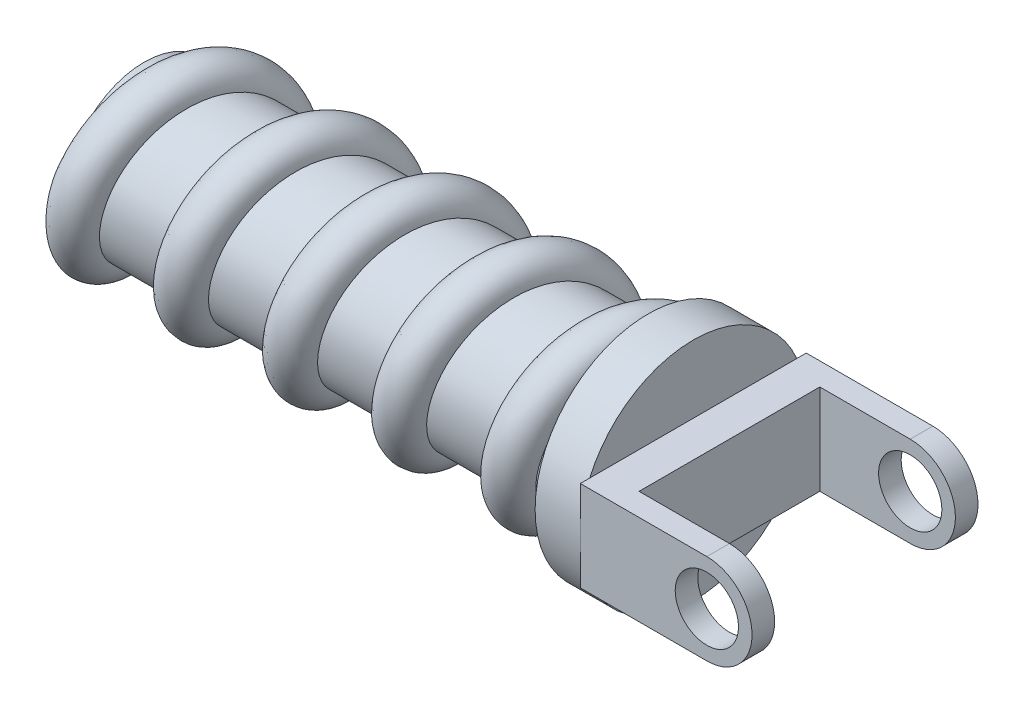
SolidWorks part; units mm, degrees
ref_plane "Front Plane" through (0, 0, 0) normal (0, 0, 1) x (1, 0, 0)
ref_plane "Top Plane" through (0, 0, 0) normal (0, 1, 0) x (1, 0, 0)
ref_plane "Right Plane" through (0, 0, 0) normal (1, 0, 0) x (0, 0, -1)
sketch "Sketch1" plane through (0, 0, 0) normal (0, 0, 1) x (1, 0, 0)
  line L1 (0, 0) -> (50.8, 0)
  line L2 (0, 0) -> (0, -5.08)
  line L3 (0, -5.08) -> (50.8, -5.08)
  line L4 (50.8, 0) -> (50.8, -5.08)
  dimension "D1" = 5.08
  dimension "D2" = 50.8
extrude "Boss-Extrude1" add sketch "Sketch1" along normal blind 7.62
sketch "Sketch2" plane through (0, 0, 7.62) normal (0, 0, 1) x (1, 0, 0)
  line L1 (0, 0) -> (0, -5.08) construction
  circle A0 centre (2.54, -2.54) radius 1.778
  point P8 (0, -2.54)
  dimension "D1" = 3.556
  dimension "D2" = 2.54
extrude "Boss-Extrude2" add sketch "Sketch2" along normal blind 5.08
sketch "Sketch3" plane through (0, 0, 0) normal (0, 0, -1) x (-1, 0, 0)
  circle A0 centre (-2.54, -2.54) radius 1.778
  dimension "D1" = 3.556
extrude "Boss-Extrude3" add sketch "Sketch3" along normal blind 5.08
sketch "Sketch4" plane through (0, 0, 7.62) normal (0, 0, 1) x (1, 0, 0)
  line L0 (0, -5.08) -> (50.8, -5.08) construction
  line L1 (50.8, 0) -> (48.768, 0)
  line L2 (50.8, 0) -> (50.8, -5.08)
  line L3 (50.8, -5.08) -> (48.768, -5.08)
  line L4 (48.768, 0) -> (48.768, -5.08)
  dimension "D1" = 2.032
extrude "Boss-Extrude4" add sketch "Sketch4" along normal blind 2.54
ref_plane "Plane1" through (0, 0, 10.16) normal (0, 0, 1) x (1, 0, 0)
sketch "Sketch5" plane through (0, 0, 10.16) normal (0, 0, 1) x (1, 0, 0)
  line L0 (48.768, -5.08) -> (50.8, -5.08) construction
  line L1 (50.8, 0) -> (55.88, 0)
  line L2 (50.8, 0) -> (50.8, -5.08)
  line L3 (50.8, -5.08) -> (55.88, -5.08)
  arc A0 (55.88, 0) -> (55.88, -5.08) centre (55.88, -2.54) cw
  dimension "D1" = 5.08
extrude "Boss-Extrude5" add sketch "Sketch5" against normal blind 1.27
sketch "Sketch6" plane through (0, 0, 0) normal (0, 0, -1) x (-1, 0, 0)
  line L0 (0, -5.08) -> (-50.8, -5.08) construction
  line L1 (-50.8, 0) -> (-48.768, 0)
  line L2 (-50.8, 0) -> (-50.8, -5.08)
  line L3 (-50.8, -5.08) -> (-48.768, -5.08)
  line L4 (-48.768, 0) -> (-48.768, -5.08)
extrude "Boss-Extrude6" add sketch "Sketch6" along normal blind 2.54
ref_plane "Plane2" through (0, 0, -2.54) normal (0, 0, -1) x (-1, 0, 0)
sketch "Sketch7" plane through (0, 0, -2.54) normal (0, 0, -1) x (-1, 0, 0)
  line L0 (-50.8, -5.08) -> (-48.768, -5.08) construction
  line L1 (-48.768, 0) -> (-55.88, 0)
  line L2 (-48.768, 0) -> (-48.768, -5.08)
  line L3 (-48.768, -5.08) -> (-55.88, -5.08)
  arc A0 (-55.88, -5.08) -> (-55.88, 0) centre (-55.88, -2.54) cw
extrude "Boss-Extrude7" add sketch "Sketch7" against normal blind 1.27
sketch "Sketch8" plane through (0, 0, -2.54) normal (0, 0, -1) x (-1, 0, 0)
  circle A0 centre (-55.88, -2.54) radius 1.778
extrude "Cut-Extrude1" cut sketch "Sketch8" against normal through all
ref_plane "Plane3" through (50.8, 0, -1.27) normal (1, 0, 0) x (0, 0, -1)
sketch "Sketch9" plane through (0, 0, 7.62) normal (0, 0, 1) x (1, 0, 0)
  line L0 (48.768, 0) -> (48.768, -5.08) construction
  line L1 (0, 0) -> (48.768, 0)
  line L2 (0, 0) -> (0, -5.08)
  line L3 (0, -5.08) -> (48.768, -5.08)
  line L4 (48.768, 0) -> (48.768, -5.08)
  line L6 (0, -5.08) -> (48.768, -5.08) construction
extrude "Cut-Extrude2" cut sketch "Sketch9" against normal through all both and the other way through all
sketch "Sketch10" plane through (48.768, 0, 0) normal (-1, 0, 0) x (0, 0, 1)
  circle A0 centre (3.81, -2.54) radius 6.35
extrude "Boss-Extrude8" add sketch "Sketch10" along normal blind 2.54
sketch "Sketch11" plane through (46.228, 0, 0) normal (-1, 0, 0) x (0, 0, 1)
  circle A0 centre (3.81, -2.54) radius 4.445
  dimension "D1" = 8.89
extrude "Boss-Extrude9" add sketch "Sketch11" along normal blind 68.961
sketch "Sketch12" plane through (46.228, 0, 0) normal (-1, 0, 0) x (0, 0, 1)
  circle A0 centre (3.81, -2.54) radius 4.445
curve "Helix/Spiral1" pitch 6.1298 height 68.96 radius 4.445 left hand yes centre (46.228, -2.54, 3.81) axis (-1, 0, 0) start towards (0, 0, -1)
sweep "Sweep1" add path "Helix/Spiral1" circular profile diameter 2.54 parameters "D3"=2.54
sketch "Sketch17" plane through (-22.733, 0, 0) normal (-1, 0, 0) x (0, 0, 1)
  circle A0 centre (3.6486, -2.5691) radius 8.1994
extrude "Cut-Extrude4" cut sketch "Sketch17" against normal blind 27.94 and the other way blind 27.94 contours A0
sketch "Sketch18" plane through (5.207, 0, 0) normal (-1, 0, 0) x (0, 0, 1)
  circle A0 centre (3.81, -2.54) radius 9.9438
extrude "Cut-Extrude5" cut sketch "Sketch18" against normal blind 12.7
